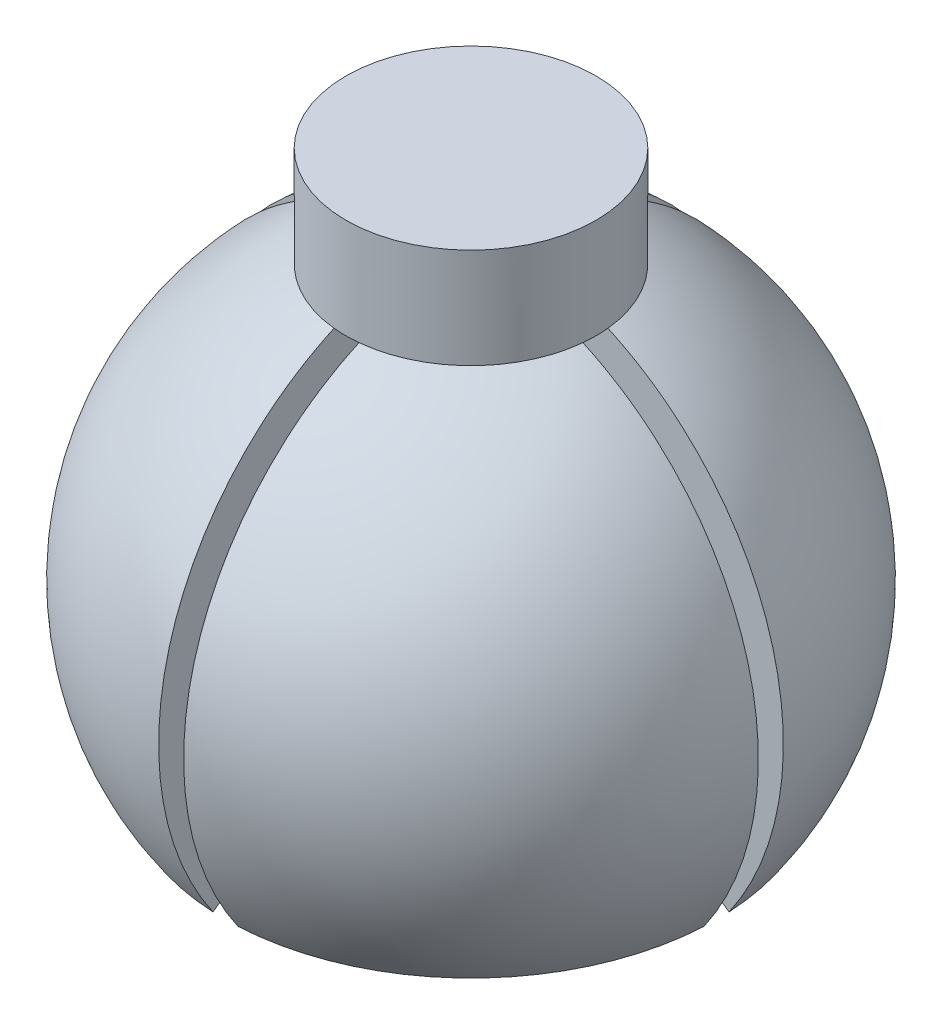
SolidWorks part; units mm, degrees
other "Markup1"
sketch "Sketch3" plane through (-5.9948, -3.4415, 5.9948) normal (0, 0, 1) x (1, 0, 0)
ref_plane "Front Plane" through (0, 0, 0) normal (0, 0, 1) x (1, 0, 0)
ref_plane "Top Plane" through (0, 0, 0) normal (0, 1, 0) x (1, 0, 0)
ref_plane "Right Plane" through (0, 0, 0) normal (1, 0, 0) x (0, 0, -1)
sketch "Sketch1" plane through (0, 0, 0) normal (0, 0, 1) x (1, 0, 0)
  line L1 (0, 7.4544) -> (0, 5)
  line L4 (4.0958, -2.8679) -> (4.9149, -3.4415)
  line L5 (0, 0) -> (3.8805, 0) construction
  line L6 (0, 0) -> (4.0958, -2.8679) construction
  line L9 (2.5, 7.4544) -> (0, 7.4544)
  line L10 (2.5, 5.4544) -> (2.5, 7.4544)
  arc A0 (4.0958, -2.8679) -> (0, 5) centre (0, 0) ccw
  arc A1 (4.9149, -3.4415) -> (2.5, 5.4544) centre (0, 0) ccw
  dimension "D1" = 5
  dimension "D2" = 12
  dimension "D3" = 35
  dimension "D4" = 2.5
  dimension "D5" = 2
revolve "Revolve1" add sketch "Sketch1" angle 360 about L1
sketch "Sketch2" plane through (0, 0, 0) normal (0, 0, 1) x (1, 0, 0)
  line L0 (-0.25, -3.4415) -> (-0.25, 5.4544)
  line L1 (-0.25, -3.4415) -> (0.25, -3.4415)
  line L2 (-0.25, 5.4544) -> (0.25, 5.4544)
  line L3 (0.25, -3.4415) -> (0.25, 5.4544)
  line L4 (4.9149, -3.4415) -> (-4.9149, -3.4415) construction
  line L5 (-2.5, 5.4544) -> (2.5, 5.4544) construction
  point P6 (0, 5.4544)
  dimension "D1" = 0.5
extrude "Cut-Extrude1" cut sketch "Sketch2" against normal blind 10
pattern_circular "CirPattern1" count 4 over 360 about axis through (0, -3.4415, 0) along (0, 1, 0) of "Cut-Extrude1"
